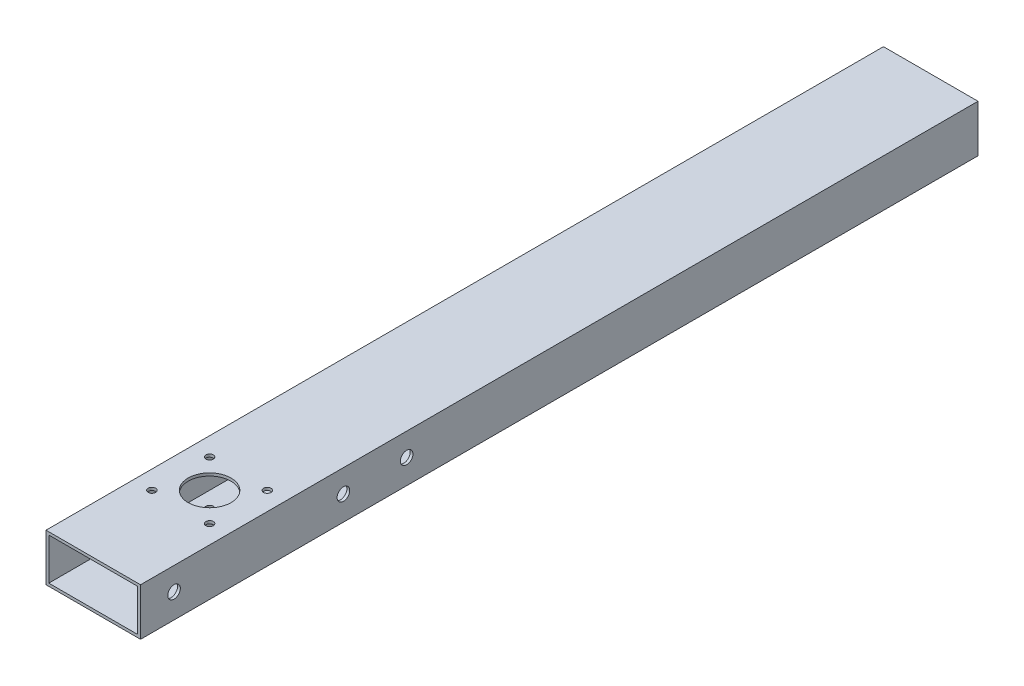
SolidWorks part; units mm, degrees
material "AISI 1015 Acero estirado en frío (SS)"
ref_plane "Alzado" through (0, 0, 0) normal (0, 0, 1) x (1, 0, 0)
ref_plane "Planta" through (0, 0, 0) normal (0, 1, 0) x (1, 0, 0)
ref_plane "Vista lateral" through (0, 0, 0) normal (1, 0, 0) x (0, 0, -1)
sketch "Croquis1" plane through (0, 0, 0) normal (0, 0, 1) x (1, 0, 0)
  line L0 (-23.9, -11.2) -> (-23.9, 11.2)
  line L1 (-25.4, -12.7) -> (25.4, -12.7)
  line L2 (-25.4, -12.7) -> (-25.4, 12.7)
  line L3 (-25.4, 12.7) -> (25.4, 12.7)
  line L4 (25.4, -12.7) -> (25.4, 12.7)
  line L5 (-25.4, -12.7) -> (25.4, 12.7) construction
  line L6 (-25.4, 12.7) -> (25.4, -12.7) construction
  line L7 (-23.9, 11.2) -> (23.9, 11.2)
  line L8 (23.9, -11.2) -> (23.9, 11.2)
  line L9 (-23.9, -11.2) -> (23.9, -11.2)
  point P0 (0, 0)
  dimension "D1" = 25.4
  dimension "D2" = 50.8
  dimension "D3" = 1.5
extrude "Saliente-Extruir1" add sketch "Croquis1" along normal blind 450
ref_plane "Plano1" through (0, -12.7, 0) normal (0, -1, 0) x (-1, 0, 0)
sketch "Croquis2" plane through (0, -12.7, 0) normal (0, -1, 0) x (-1, 0, 0)
  line L0 (0, -450) -> (0, -222.1085) construction
  line L1 (25.4, -450) -> (-25.4, -450) construction
  line L2 (25.4, -387.5) -> (-25.4, -387.5) construction
  line L3 (25.4, -450) -> (25.4, 0) construction
  line L4 (-25.4, -450) -> (-25.4, 0) construction
  circle A0 centre (0, -387.5) radius 11.5
  circle A1 centre (15.5, -403) radius 2
  circle A2 centre (-15.5, -403) radius 2
  circle A3 centre (-15.5, -372) radius 2
  circle A4 centre (15.5, -372) radius 2
  dimension "D3" = 23
  dimension "D4" = 4
  dimension "D1" = 62.5
  dimension "D2" = 15.5
  dimension "D5" = 15.5
extrude "Cortar-Extruir1" cut sketch "Croquis2" against normal blind 26
hole_wizard "Taladro de margen para 1/41" positions "Croquis3" profile "Croquis4" hole size "1/4" standard "Ansi Inch" end condition through all
sketch "Croquis3" plane through (-25.4, 197.8886, 162.9891) normal (-1, 0, 0) x (0, -1, 0)
  point P0 (197.4886, 269.0109)
  point P3 (197.4886, 178.0109)
  point P6 (197.4886, 144.0109)
  point P9 (572.8886, 144.0109)
  point P12 (572.8886, 178.0109)
  point P15 (572.8886, 269.0109)
  point P19 (197.4886, 269.0109)
  point P21 (197.4886, 144.0109)
sketch "Croquis4" plane through (-25.4, 0.4, 432) normal (0, 1, 0) x (0, 0, 1)
  line L0 (0, 0) -> (0, 50.8)
  line L1 (0, 50.8) -> (3.3782, 50.8)
  line L2 (3.3782, 50.8) -> (3.3782, 0)
  line L3 (3.3782, 0) -> (0, 0)
  line L4 (0, -6.35) -> (0, 107.95) construction
  dimension "Diámetro de taladro hasta el siguiente" = 6.7564
  dimension "Profundidad de taladro hasta el siguiente" = 50.8
